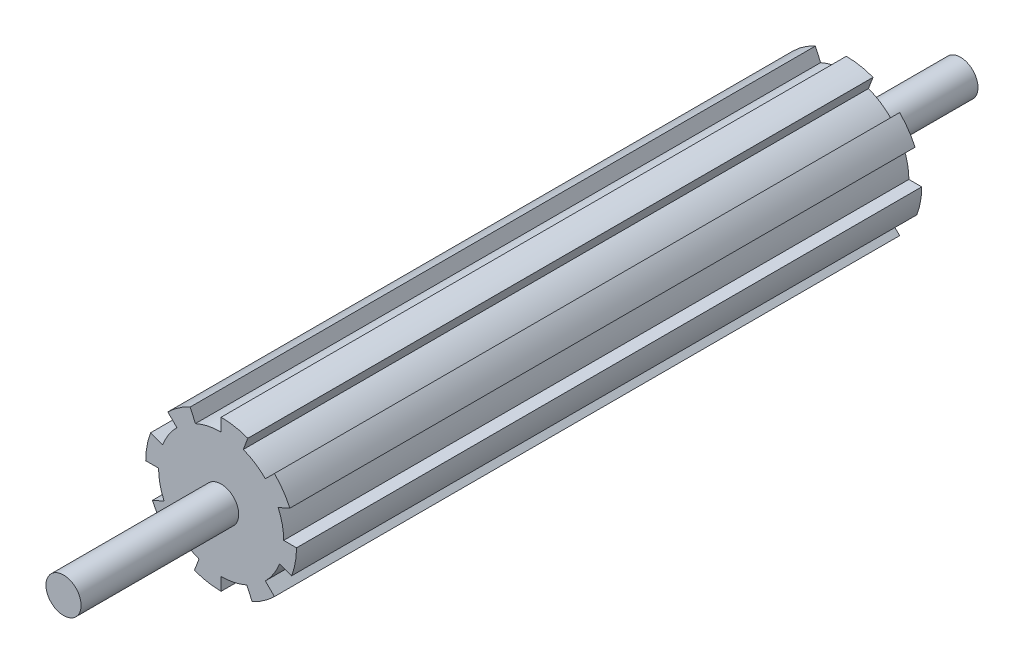
SolidWorks part; units mm, degrees
material "Ductile Iron"
ref_plane "Front Plane" through (0, 0, 0) normal (0, 0, 1) x (1, 0, 0)
ref_plane "Top Plane" through (0, 0, 0) normal (0, 1, 0) x (1, 0, 0)
ref_plane "Right Plane" through (0, 0, 0) normal (1, 0, 0) x (0, 0, -1)
sketch "Sketch1" plane through (0, 0, 0) normal (0, 0, 1) x (1, 0, 0)
  line L0 (0, 3.5604) -> (0, 4.2915)
  line L2 (1.5197, 4.0134) -> (1.2608, 3.3297)
  line L3 (3.9125, 1.7633) -> (3.246, 1.4629)
  line L4 (2.5176, 2.5176) -> (3.0345, 3.0345)
  line L6 (4.0134, -1.5197) -> (3.3297, -1.2608)
  line L7 (3.5604, 0) -> (4.2915, 0)
  line L9 (1.7633, -3.9125) -> (1.4629, -3.246)
  line L10 (2.5176, -2.5176) -> (3.0345, -3.0345)
  line L12 (-1.5197, -4.0134) -> (-1.2608, -3.3297)
  line L13 (0, -3.5604) -> (0, -4.2915)
  line L15 (-3.9125, -1.7633) -> (-3.246, -1.4629)
  line L16 (-2.5176, -2.5176) -> (-3.0345, -3.0345)
  line L18 (-4.0134, 1.5197) -> (-3.3297, 1.2608)
  line L19 (-3.5604, 0) -> (-4.2915, 0)
  line L21 (-1.7633, 3.9125) -> (-1.4629, 3.246)
  line L22 (-2.5176, 2.5176) -> (-3.0345, 3.0345)
  arc A2 (-2.5176, 2.5176) -> (-3.3297, 1.2608) centre (0, 0) ccw
  arc A3 (-1.7633, 3.9125) -> (-3.0345, 3.0345) centre (0, 0) ccw
  arc A4 (-4.0134, 1.5197) -> (-4.2915, 0) centre (0, 0) ccw
  arc A5 (-3.5604, 0) -> (-3.246, -1.4629) centre (0, 0) ccw
  arc A6 (-3.9125, -1.7633) -> (-3.0345, -3.0345) centre (0, 0) ccw
  arc A7 (-2.5176, -2.5176) -> (-1.2608, -3.3297) centre (0, 0) ccw
  arc A8 (-1.5197, -4.0134) -> (0, -4.2915) centre (0, 0) ccw
  arc A9 (0, -3.5604) -> (1.4629, -3.246) centre (0, 0) ccw
  arc A10 (1.7633, -3.9125) -> (3.0345, -3.0345) centre (0, 0) ccw
  arc A11 (2.5176, -2.5176) -> (3.3297, -1.2608) centre (0, 0) ccw
  arc A12 (4.0134, -1.5197) -> (4.2915, 0) centre (0, 0) ccw
  arc A13 (3.5604, 0) -> (3.246, 1.4629) centre (0, 0) ccw
  arc A14 (3.9125, 1.7633) -> (3.0345, 3.0345) centre (0, 0) ccw
  arc A15 (2.5176, 2.5176) -> (1.2608, 3.3297) centre (0, 0) ccw
  arc A16 (1.5197, 4.0134) -> (0, 4.2915) centre (0, 0) ccw
  arc A17 (0, 3.5604) -> (-1.4629, 3.246) centre (0, 0) ccw
  point P25 (0, 0)
  dimension "D1" = 8
extrude "Boss-Extrude1" add sketch "Sketch1" along normal blind 35.5859
sketch "Sketch2" plane through (0, 0, 35.5859) normal (0, 0, 1) x (1, 0, 0)
  circle A0 centre (0, 0) radius 1
extrude "Boss-Extrude2" add sketch "Sketch2" along normal blind 8.97
sketch "Sketch3" plane through (0, 0, 0) normal (0, 0, -1) x (-1, 0, 0)
  circle A0 centre (0, 0) radius 1
extrude "Boss-Extrude3" add sketch "Sketch3" along normal blind 6.4942 contours A0
ref_axis "R-axis" through (0, 0, 52.5744) along (0, 0, -1)
